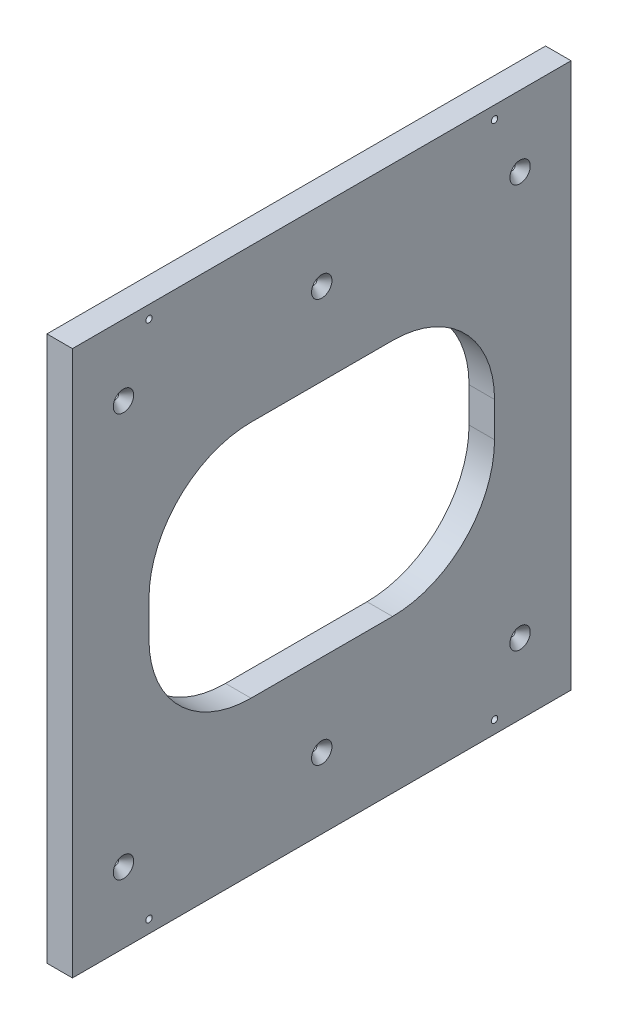
SolidWorks part; units mm, degrees
material "Beech"
ref_plane "Front Plane" through (0, 0, 0) normal (0, 0, 1) x (1, 0, 0)
ref_plane "Top Plane" through (0, 0, 0) normal (0, 1, 0) x (1, 0, 0)
ref_plane "Right Plane" through (0, 0, 0) normal (1, 0, 0) x (0, 0, -1)
sketch "Sketch1" plane through (0, 0, 0) normal (0, 0, 1) x (1, 0, 0)
  line L0 (-234.753, -188.5238) -> (-91.9973, -188.5238) construction
  line L1 (-234.753, 82.8417) -> (-222.053, 82.8417)
  line L2 (-234.753, 82.8417) -> (-234.753, -188.5238)
  line L3 (-234.753, -188.5238) -> (-222.053, -188.5238)
  line L4 (-222.053, 82.8417) -> (-222.053, -188.5238)
  dimension "D1" = 12.7
extrude "Boss-Extrude1" add sketch "Sketch1" along normal offset from surface (248.25 mm away) 19.05
sketch "Sketch2" plane through (-234.753, 0, 0) normal (-1, 0, 0) x (0, 0, 1)
  line L0 (124.125, 82.8417) -> (124.125, -52.841) construction
  line L1 (248.25, 82.8417) -> (0, 82.8417) construction
  line L2 (124.125, -52.841) -> (248.25, -52.841) construction
  line L3 (248.25, 82.8417) -> (248.25, -188.5238) construction
  line L5 (38.1, -112.3238) -> (210.15, -112.3238)
  line L6 (38.1, -112.3238) -> (38.1, 6.6417)
  line L7 (38.1, 6.6417) -> (210.15, 6.6417)
  line L8 (210.15, -112.3238) -> (210.15, 6.6417)
  line L9 (38.1, -112.3238) -> (210.15, 6.6417) construction
  line L10 (38.1, 6.6417) -> (210.15, -112.3238) construction
  dimension "D1" = 38.1
  dimension "D2" = 76.2
extrude "Cut-Extrude1" cut sketch "Sketch2" against normal through all
fillet "Fillet1" radius 50.8 4 edges at (-228.403, 6.6417, 38.1) (-228.403, -112.3238, 38.1) (-228.403, -112.3238, 210.15) (-228.403, 6.6417, 210.15)
hole_wizard "Hole1" positions "Sketch3" profile "Sketch4" legacy
sketch "Sketch3" plane through (181.0394, -52.975, -12.7) normal (0, 0, -1) x (0, -1, 0)
  line L0 (-129.4667, 415.7924) -> (-129.4667, 273.0368) construction
  line L5 (-135.8167, 409.4424) -> (135.5488, 409.4424) construction
  line L10 (-135.8167, 279.3868) -> (135.5488, 279.3868) construction
  line L11 (-0.134, 409.4424) -> (-0.134, 279.3868) construction
  point P22 (-129.4667, 384.0424)
  point P24 (-129.4667, 304.7868)
  point P26 (-110.4167, 409.4424)
  point P30 (-0.134, 409.4424)
  point P50 (110.1488, 409.4424)
  point P51 (129.1988, 304.7868)
  point P52 (129.1988, 384.0424)
sketch "Sketch4" plane through (-203.003, -182.1738, -12.7) normal (1, 0, 0) x (0, 1, 0)
  line L0 (0, 0) -> (0, 32.7039)
  line L1 (0, 32.7039) -> (1.5875, 31.75)
  line L2 (1.5875, 31.75) -> (1.5875, 4.0177)
  line L3 (1.5875, 4.0177) -> (5.08, 0)
  line L4 (5.08, 0) -> (0, 0)
  line L5 (0, -14.3089) -> (0, 102.4216) construction
  line L6 (0, 32.7039) -> (-1.5875, 31.75) construction
  line L7 (-1.5875, 4.0177) -> (-5.08, 0) construction
  dimension "Diameter" = 3.175
  dimension "Depth" = 31.75
  dimension "C-Sink Diameter" = 10.16
  dimension "C-Sink Angle" = 82
  dimension "Drill Angle" = 118
hole_wizard "Hole2" positions "Sketch5" profile "Sketch6" legacy
sketch "Sketch5" plane through (-234.753, -52.975, -1090.5128) normal (-1, 0, 0) x (0, -1, 0)
  line L3 (-0.134, 1338.7628) -> (-0.134, 1090.5128) construction
  point P1 (-129.4667, 1300.6628)
  point P3 (-129.4667, 1128.6128)
  point P15 (129.1988, 1128.6128)
  point P16 (129.1988, 1300.6628)
sketch "Sketch6" plane through (-234.753, 76.4917, 210.15) normal (0, 1, 0) x (0, 0, 1)
  line L0 (0, 0) -> (0, 32.7039)
  line L1 (0, 32.7039) -> (1.5875, 31.75)
  line L2 (1.5875, 31.75) -> (1.5875, 4.0177)
  line L3 (1.5875, 4.0177) -> (5.08, 0)
  line L4 (5.08, 0) -> (0, 0)
  line L5 (0, -14.3089) -> (0, 102.4216) construction
  line L6 (0, 32.7039) -> (-1.5875, 31.75) construction
  line L7 (-1.5875, 4.0177) -> (-5.08, 0) construction
  dimension "Diameter" = 3.175
  dimension "Depth" = 31.75
  dimension "C-Sink Diameter" = 10.16
  dimension "C-Sink Angle" = 82
  dimension "Drill Angle" = 118
hole_wizard "Hole3" positions "Sketch7" profile "Sketch8" legacy
sketch "Sketch7" plane through (-222.053, -52.975, -1090.5128) normal (1, 0, 0) x (0, 1, 0)
  line L0 (100.6, 1338.7628) -> (100.6, 1090.5128) construction
  line L6 (0.134, 1338.7628) -> (0.134, 1090.5128) construction
  point P12 (100.6, 1313.3628)
  point P14 (100.6, 1115.9128)
  point P16 (100.6, 1214.6378)
  point P22 (-100.332, 1214.6378)
  point P23 (-100.332, 1115.9128)
  point P24 (-100.332, 1313.3628)
sketch "Sketch8" plane through (-222.053, -153.307, 222.85) normal (0, 1, 0) x (0, 0, -1)
  line L0 (0, 0) -> (0, 32.7039)
  line L1 (0, 32.7039) -> (1.5875, 31.75)
  line L2 (1.5875, 31.75) -> (1.5875, 4.0177)
  line L3 (1.5875, 4.0177) -> (5.08, 0)
  line L4 (5.08, 0) -> (0, 0)
  line L5 (0, -14.3089) -> (0, 102.4216) construction
  line L6 (0, 32.7039) -> (-1.5875, 31.75) construction
  line L7 (-1.5875, 4.0177) -> (-5.08, 0) construction
  dimension "Diameter" = 3.175
  dimension "Depth" = 31.75
  dimension "C-Sink Diameter" = 10.16
  dimension "C-Sink Angle" = 82
  dimension "Drill Angle" = 118
